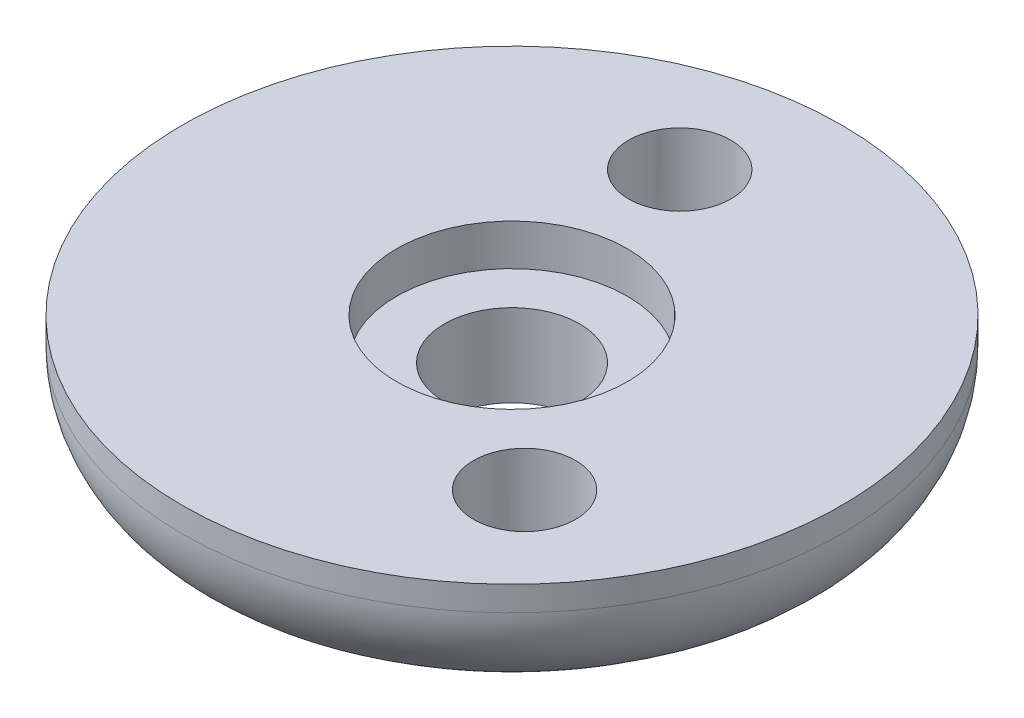
SolidWorks part; units mm, degrees
ref_plane "Front Plane" through (0, 0, 0) normal (0, 0, 1) x (1, 0, 0)
ref_plane "Top Plane" through (0, 0, 0) normal (0, 1, 0) x (1, 0, 0)
ref_plane "Right Plane" through (0, 0, 0) normal (1, 0, 0) x (0, 0, -1)
sketch "Sketch1" plane through (0, 0, 0) normal (0, 1, 0) x (1, 0, 0)
  circle A0 centre (0, 0) radius 10
  dimension "D1" = 20
extrude "Boss-Extrude1" add sketch "Sketch1" along normal blind 3 and the other way blind 10
ref_axis "5hubaxis" through (0, 5.5, 0) along (0, -1, 0)
ref_plane "holeplane" through (-3.3529, -1.0931, 1.8877) normal (0.8382, 0.2733, -0.4719) x (-0.4487, -0.1463, -0.8816)
sketch "Sketch4" plane through (-3.3529, -1.0931, 1.8877) normal (0.8382, 0.2733, -0.4719) x (-0.4487, -0.1463, -0.8816)
  circle A0 centre (0, 0) radius 1.5 construction
  circle A1 centre (0, 0) radius 1.5
extrude "hole" cut sketch "Sketch4" against normal through all
pattern_circular "holecir" count 5 over 360 about axis through (0, 5.5, 0) along (0, -1, 0) of "hole"
sketch "Sketch5" plane through (0, -10, 0) normal (0, -1, 0) x (1, 0, 0)
  line L0 (-10, 0) -> (10, 0) construction
  circle A0 centre (0, 0) radius 10 construction
  text T0 "5"
extrude "Boss-Extrude2" [suppressed] add sketch "Sketch5" along normal blind 1
ref_plane "Plane1" through (0, -5, 0) normal (0, -1, 0) x (-1, 0, 0)
sketch "Sketch6" plane through (0, -5, 0) normal (0, -1, 0) x (-1, 0, 0)
  circle A0 centre (0, 0) radius 3.5
  dimension "D1" = 7
extrude "bearinghole" cut sketch "Sketch6" along normal blind 2.5
sketch "Sketch7" plane through (0, -5, 0) normal (0, -1, 0) x (-1, 0, 0)
  circle A0 centre (0, 0) radius 2.05
  dimension "D1" = 4.1
extrude "shafthole" cut sketch "Sketch7" along normal through all
sketch "Sketch8" plane through (0, 3, 0) normal (0, 1, 0) x (1, 0, 0)
  line L0 (-1.9732, 9.8034) -> (0, 0) construction
  line L1 (0, 0) -> (7.3586, -6.7713) construction
  line L2 (0, 0) -> (1.9732, -9.8034) construction
  line L3 (3.4214, -9.3965) -> (2.2297, -3.4761) construction
  line L4 (0, 0) -> (9.9333, -1.1528) construction
  line L5 (9.9939, 0.3502) -> (3.995, 1.0464) construction
  line L6 (0, 0) -> (4.166, 9.0909) construction
  line L7 (2.7552, 9.613) -> (0.2393, 4.1229) construction
  circle A0 centre (0, 0) radius 10 construction
  circle A1 centre (0, 0) radius 6.5 construction
  point P15 (-1.2826, 6.3722)
  point P16 (4.7831, -4.4014)
  dimension "D3" = 13
  dimension "D1" = 36
  dimension "D2" = 36
hole_wizard "Ø3.1 (3.1) Diameter Hole1" positions "Sketch9" profile "Sketch10" hole size "Ø3.1" standard "ISO" end condition through all
sketch "Sketch9" plane through (0, 3, 0) normal (0, 1, 0) x (1, 0, 0)
  point P0 (-1.2826, 6.3722)
  point P3 (4.7831, -4.4014)
sketch "Sketch10" plane through (-1.2826, 3, -6.3722) normal (1, 0, 0) x (0, 0, 1)
  line L0 (0, 0) -> (0, 13)
  line L1 (0, 13) -> (1.55, 13)
  line L2 (1.55, 13) -> (1.55, 0)
  line L5 (1.55, 0) -> (0, 0)
  line L11 (0, -6.35) -> (0, 107.95) construction
  dimension "Thru Hole Dia." = 3.1
  dimension "Thru Hole Depth" = 13
fillet "Fillet2" radius 3 2 edges at (0, 3, 10) (0, -10, 10)
ref_plane "Plane2" through (0, -6.25, 0) normal (0, -1, 0) x (-1, 0, 0)
sketch "Sketch11" plane through (0, -6.25, 0) normal (0, -1, 0) x (-1, 0, 0)
  circle A0 centre (0, 0) radius 10
extrude "Cut-Extrude1" cut sketch "Sketch11" against normal blind 10
